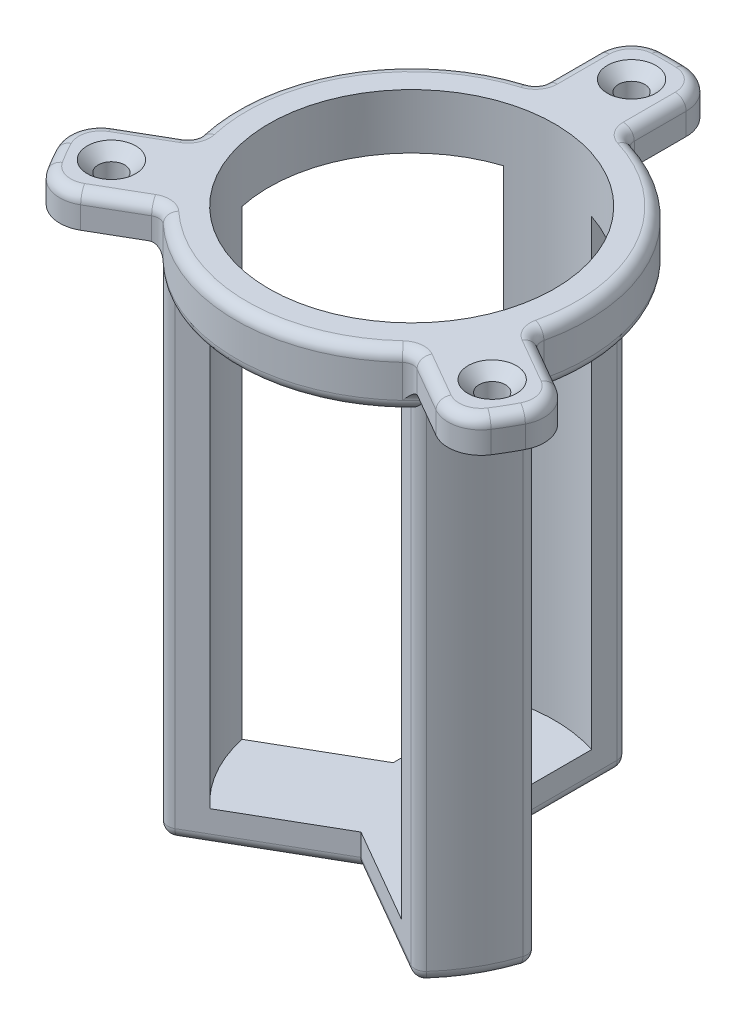
SolidWorks part; units mm, degrees
ref_plane "Plano frontal" through (0, 0, 0) normal (0, 0, 1) x (1, 0, 0)
ref_plane "Plano superior" through (0, 0, 0) normal (0, 1, 0) x (1, 0, 0)
ref_plane "Plano direito" through (0, 0, 0) normal (1, 0, 0) x (0, 0, -1)
sketch "Esboço1" plane through (0, 0, 0) normal (0, 1, 0) x (1, 0, 0)
  line L0 (0, 0) -> (0, 16) construction
  line L1 (0, 0) -> (13.8564, -8) construction
  line L2 (0, 0) -> (-13.8564, -8) construction
  line L3 (-11.4164, -11.2101) -> (0, -4.6188)
  line L4 (0, -4.6188) -> (11.4164, -11.2101)
  line L5 (-15.4164, -4.2819) -> (-4, 2.3094)
  line L6 (-4, 2.3094) -> (-4, 15.4919)
  line L8 (4, 2.3094) -> (15.4164, -4.2819)
  line L9 (4, 15.4919) -> (4, 2.3094)
  arc A0 (-4, 15.4919) -> (4, 15.4919) centre (0, 0) ccw construction
  arc A3 (11.4164, -11.2101) -> (15.4164, -4.2819) centre (0, 0) ccw
  arc A5 (12.7121, -2.7206) -> (4, 12.3693) centre (0, 0) ccw construction
  arc A7 (-11.4164, -11.2101) -> (-15.4164, -4.2819) centre (0, 0) cw
  arc A8 (-4, 12.3693) -> (-12.7121, -2.7206) centre (0, 0) ccw construction
  arc A9 (-8.7121, -9.6488) -> (8.7121, -9.6488) centre (0, 0) ccw construction
  arc A10 (-4, 15.4919) -> (4, 15.4919) centre (0, 0) cw
  dimension "D1" = 32
  dimension "D2" = 26
  dimension "D6" = 8
  dimension "D3" = 8
  dimension "D4" = 120
  dimension "D5" = 120
  dimension "D7" = 8
extrude "Ressalto-extrusão1" add sketch "Esboço1" along normal blind 3
sketch "Esboço2" plane through (0, 3, 0) normal (0, 1, 0) x (1, 0, 0)
  line L0 (0, -4.6188) -> (11.4164, -11.2101) construction
  line L1 (-4, 15.4919) -> (-4, 2.3094) construction
  line L2 (4, 2.3094) -> (4, 15.4919) construction
  line L3 (15.4164, -4.2819) -> (4, 2.3094) construction
  line L4 (-11.4164, -11.2101) -> (0, -4.6188) construction
  line L5 (-4, 2.3094) -> (-15.4164, -4.2819) construction
  line L6 (-4, 15.4919) -> (-4, 12.3693)
  line L7 (4, 15.4919) -> (4, 12.3693)
  line L8 (12.7121, -2.7206) -> (15.4164, -4.2819)
  line L9 (11.4164, -11.2101) -> (8.7121, -9.6488)
  line L10 (-8.7121, -9.6488) -> (-11.4164, -11.2101)
  line L11 (-15.4164, -4.2819) -> (-12.7121, -2.7206)
  arc A0 (-11.4164, -11.2101) -> (-15.4164, -4.2819) centre (0, 0) cw
  arc A1 (-15.4164, -4.2819) -> (-11.4164, -11.2101) centre (0, 0) ccw construction
  arc A2 (15.4164, -4.2819) -> (11.4164, -11.2101) centre (0, 0) cw
  arc A3 (-4, 12.3693) -> (4, 12.3693) centre (0, 0) cw
  arc A4 (-4, 15.4919) -> (4, 15.4919) centre (0, 0) cw
  arc A5 (4, 15.4919) -> (-4, 15.4919) centre (0, 0) ccw construction
  arc A6 (12.7121, -2.7206) -> (8.7121, -9.6488) centre (0, 0) cw
  arc A7 (-8.7121, -9.6488) -> (-12.7121, -2.7206) centre (0, 0) cw
  dimension "D1" = 13
extrude "Ressalto-extrusão2" add sketch "Esboço2" along normal blind 42
sketch "Esboço3" plane through (0, 45, 0) normal (0, 1, 0) x (1, 0, 0)
  circle A0 centre (0, 0) radius 16
  circle A1 centre (0, 0) radius 13
  dimension "D1" = 32
  dimension "D2" = 26
extrude "Ressalto-extrusão3" add sketch "Esboço3" along normal blind 5
sketch "Esboço5" plane through (0, 50, 0) normal (0, 1, 0) x (1, 0, 0)
  line L0 (-8.7121, -9.6488) -> (-16.1659, -13.9522)
  line L1 (-12.7121, -2.7206) -> (-20.1659, -7.024)
  line L2 (-4, 2.3094) -> (-12.7121, -2.7206) construction
  line L3 (8.7121, -9.6488) -> (16.1659, -13.9522)
  line L4 (12.7121, -2.7206) -> (20.1659, -7.024)
  line L5 (4, 12.3693) -> (4, 20.9762)
  line L6 (-4, 12.3693) -> (-4, 20.9762)
  line L7 (-8.7121, -9.6488) -> (0, -4.6188) construction
  line L8 (0, -4.6188) -> (8.7121, -9.6488) construction
  line L9 (12.7121, -2.7206) -> (4, 2.3094) construction
  arc A0 (-21.3325, -10.9966) -> (-20.1896, -12.9761) centre (0, 0) ccw
  circle A1 centre (0, 0) radius 13 construction
  arc A2 (4, 12.3693) -> (-4, 12.3693) centre (0, 0) ccw
  arc A3 (-12.7121, -2.7206) -> (-8.7121, -9.6488) centre (0, 0) ccw
  arc A4 (1.1429, 23.9728) -> (-1.1429, 23.9728) centre (0, 0) ccw
  arc A5 (8.7121, -9.6488) -> (12.7121, -2.7206) centre (0, 0) ccw
  arc A6 (20.1896, -12.9761) -> (21.3325, -10.9966) centre (0, 0) ccw
  arc A7 (-4, 20.9762) -> (-1.1429, 23.9728) centre (-1, 20.9762) cw
  arc A8 (4, 20.9762) -> (1.1429, 23.9728) centre (1, 20.9762) ccw
  arc A9 (20.1659, -7.024) -> (21.3325, -10.9966) centre (18.6659, -9.6221) cw
  arc A10 (16.1659, -13.9522) -> (20.1896, -12.9761) centre (17.6659, -11.3541) ccw
  arc A11 (-16.1659, -13.9522) -> (-20.1896, -12.9761) centre (-17.6659, -11.3541) cw
  arc A12 (-20.1659, -7.024) -> (-21.3325, -10.9966) centre (-18.6659, -9.6221) ccw
  point P35 (4, 23.6643)
  point P40 (18.4939, -15.2963)
  dimension "D1" = 48
  dimension "D2" = 3
extrude "Ressalto-extrusão4" add sketch "Esboço5" against normal blind 3
fillet "Filete3" radius 1 45 edges at (0, 50, -24) (-20.7846, 50, 12) (20.7846, 50, 12) (3.1712, 50, -23.0464) (-3.1712, 50, -23.0464) (-21.5444, 50, 8.7768) (-18.3731, 50, 14.2696) (18.3731, 50, 14.2696) (21.5444, 50, 8.7768) (4, 50, -18.2341) (-4, 50, -18.2341) (-17.7912, 50, 5.6529) (-13.7912, 50, 12.5811) (13.7912, 50, 12.5811) (17.7912, 50, 5.6529) (-4, 0, -8.9007) (-9.7082, 0, 0.9862) (-5.7082, 0, 7.9144) (5.7082, 0, 7.9144) (9.7082, 0, 0.9862) (4, 0, -8.9007) (11.4164, 22.5, 11.2101) (0, 45, 16) (-11.4164, 22.5, 11.2101) (-13.8564, 0, 8) (-15.4164, 22.5, 4.2819) (-13.8564, 45, -8) (-4, 22.5, -15.4919) (0, 0, -16) (4, 22.5, -15.4919) (13.8564, 45, -8) (15.4164, 22.5, 4.2819) (13.8564, 0, 8) (4, 48.5, -15.4919) (0, 47, -16) (-4, 48.5, -15.4919) (-13.8564, 50, -8) (-15.4164, 48.5, 4.2819) (-13.8564, 47, 8) (-11.4164, 48.5, 11.2101) (0, 50, 16) (11.4164, 48.5, 11.2101) (13.8564, 47, 8) (15.4164, 48.5, 4.2819) (13.8564, 50, -8)
sketch "Esboço6" plane through (0, 50, 0) normal (0, 1, 0) x (1, 0, 0)
  line L0 (0, 0) -> (0, 20) construction
  line L1 (0, 0) -> (17.3205, -10) construction
  line L2 (0, 0) -> (-17.3205, -10) construction
  point P4 (0, 20)
  dimension "D1" = 20
  dimension "D2" = 3
hole_wizard "Escareado para parafuso com cabeça escareada chata de M21" positions "3DSketch2" profile "Esboço8" countersink size "M2" standard "ISO" end condition up to next
sketch3d "3DSketch2"
  point P0 (0, 50, -20)
  point P3 (17.3205, 50, 10)
  point P6 (-17.3205, 50, 10)
sketch "Esboço8" plane through (0, 50, -20) normal (1, 0, 0) x (0, 0, 1)
  line L0 (0, 0) -> (0, 3)
  line L1 (0, 3) -> (1.2, 3)
  line L2 (1.2, 3) -> (1.2, 1)
  line L3 (1.2, 1) -> (2.2, 0)
  line L5 (2.2, 0) -> (0, 0)
  line L6 (-1.2, 1) -> (-2.2, 0) construction
  line L11 (0, -6.35) -> (0, 107.95) construction
  dimension "Thru Hole Dia." = 2.4
  dimension "Thru Hole Depth" = 3
  dimension "Near C'Sink Dia." = 4.4
  dimension "Near C'Sink Angle" = 90
